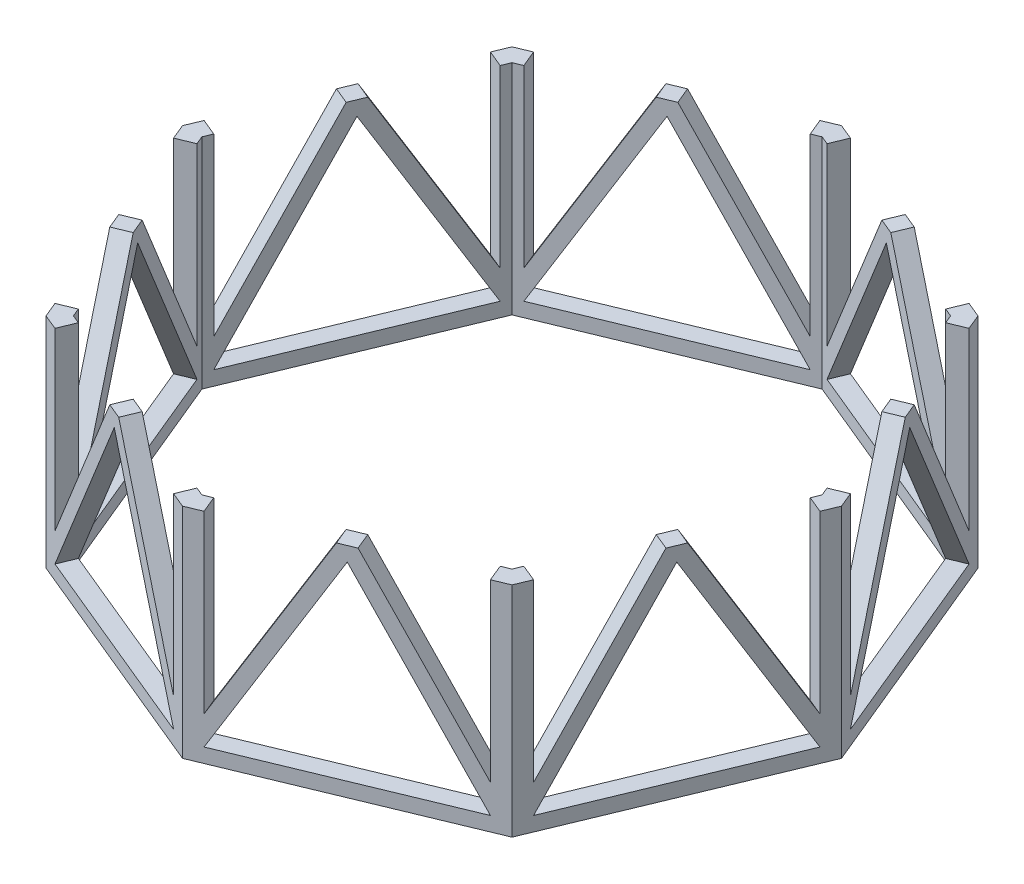
SolidWorks part; units mm, degrees
ref_plane "Front Plane" through (0, 0, 0) normal (0, 0, 1) x (1, 0, 0)
ref_plane "Top Plane" through (0, 0, 0) normal (0, 1, 0) x (1, 0, 0)
ref_plane "Right Plane" through (0, 0, 0) normal (1, 0, 0) x (0, 0, -1)
sketch "Sketch1" plane through (0, 0, 0) normal (0, 1, 0) x (1, 0, 0)
  line L1 (2164.7844, 0) -> (1530.7337, 1530.7337)
  line L2 (1530.7337, 1530.7337) -> (0, 2164.7844)
  line L3 (0, 2164.7844) -> (-1530.7337, 1530.7337)
  line L4 (-1530.7337, 1530.7337) -> (-2164.7844, 0)
  line L5 (-2164.7844, 0) -> (-1530.7337, -1530.7337)
  line L6 (-1530.7337, -1530.7337) -> (0, -2164.7844)
  line L7 (0, -2164.7844) -> (1530.7337, -1530.7337)
  line L8 (1530.7337, -1530.7337) -> (2164.7844, 0)
  line L9 (2300.0834, 0) -> (1626.4046, 1626.4046)
  line L10 (1626.4046, 1626.4046) -> (0, 2300.0834)
  line L11 (0, 2300.0834) -> (-1626.4046, 1626.4046)
  line L12 (-1626.4046, 1626.4046) -> (-2300.0834, 0)
  line L13 (-2300.0834, 0) -> (-1626.4046, -1626.4046)
  line L14 (-1626.4046, -1626.4046) -> (0, -2300.0834)
  line L15 (0, -2300.0834) -> (1626.4046, -1626.4046)
  line L16 (1626.4046, -1626.4046) -> (2300.0834, 0)
  circle A0 centre (0, 0) radius 2000 construction
  circle A1 centre (0, 0) radius 2125 construction
  dimension "D1" = 4000
  dimension "D2" = 4250
extrude "Boss-Extrude1" add sketch "Sketch1" along normal blind 100
sketch "Sketch2" plane through (813.2023, 0, 1963.244) normal (0.3827, 0, 0.9239) x (0.9239, 0, -0.3827)
  line L1 (-57.735, 1525.0687) -> (-765.0288, 300)
  line L3 (765.0288, 300) -> (57.735, 1525.0687)
  line L4 (-765.0288, 100) -> (0, 1425.0687)
  line L5 (0, 1425.0687) -> (765.0288, 100)
  line L7 (-57.735, 1525.0687) -> (57.735, 1525.0687)
  line L9 (-880.4988, 100) -> (-765.0288, 100)
  line L10 (-880.4988, 100) -> (-880.4988, 1525.0687)
  line L11 (-880.4988, 1525.0687) -> (-765.0288, 1525.0687)
  line L12 (-765.0288, 300) -> (-765.0288, 1525.0687)
  line L13 (765.0288, 100) -> (880.4988, 100)
  line L14 (765.0288, 300) -> (765.0288, 1525.0687)
  line L15 (765.0288, 1525.0687) -> (880.4988, 1525.0687)
  line L16 (880.4988, 100) -> (880.4988, 1525.0687)
  line L17 (-880.4988, 100) -> (-765.0288, 100) [skipped]
  circle A0 centre (0, 608.3562) radius 508.3562 construction
  dimension "D1" = 1760.9977
  dimension "D3" = 100
  dimension "D4" = 100
extrude "Boss-Extrude2" add sketch "Sketch2" against normal blind 125
ref_axis "Axis1" through (0, 1601.3222, 0) along (0, -1, 0)
pattern_circular "CirPattern1" count 8 over 360 about axis through (0, 1601.3222, 0) along (0, -1, 0) of "Boss-Extrude2"
